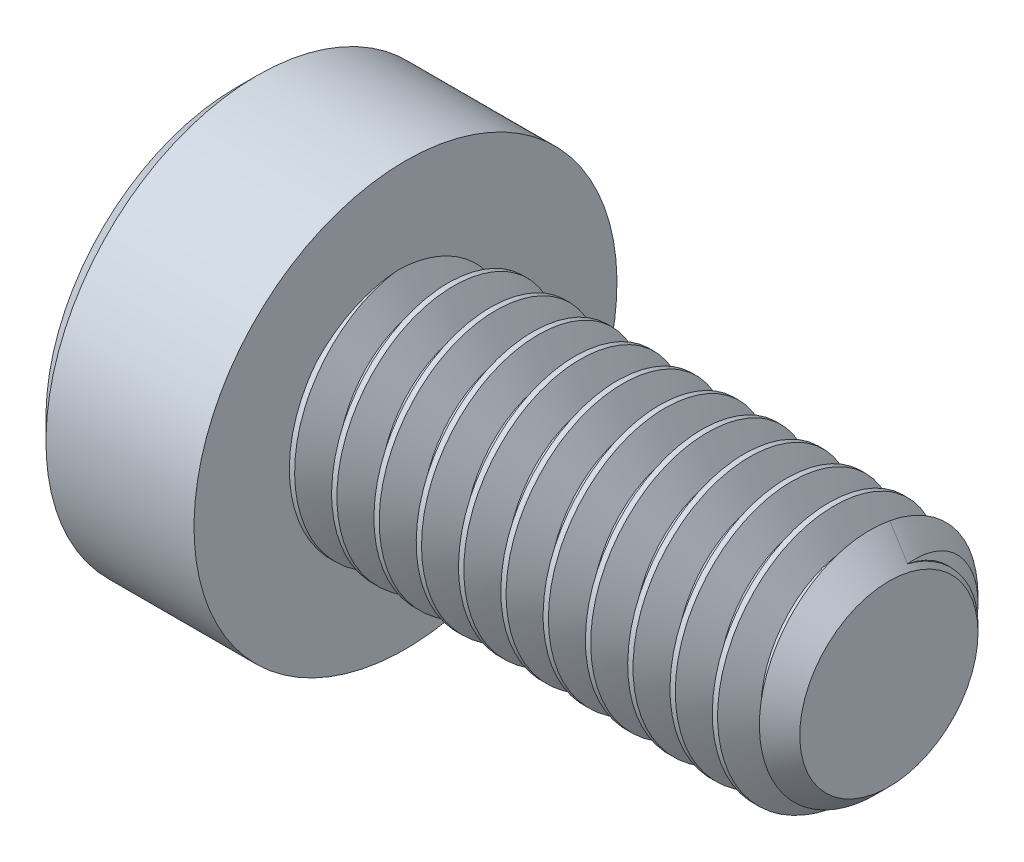
SolidWorks part; units mm, degrees
ref_plane "Front Plane" through (0, 0, 0) normal (0, 0, 1) x (1, 0, 0)
ref_plane "Top Plane" through (0, 0, 0) normal (0, 1, 0) x (1, 0, 0)
ref_plane "Right Plane" through (0, 0, 0) normal (1, 0, 0) x (0, 0, -1)
sketch "Sketch1" plane through (0, 0, 0) normal (0, 0, 1) x (1, 0, 0)
  line L0 (4, 0) -> (-4, 0) construction
  line L1 (4, 2) -> (4, -2) construction
  line L2 (-4, 3.5) -> (-4, -3.5) construction
  line L3 (-4, 3.5) -> (-6.45, 3.5) construction
  line L4 (-6.45, 3.5) -> (-6.8, 3.15) construction
  line L5 (-6.8, 3.15) -> (-6.8, -3.15) construction
  line L6 (-6.8, -3.15) -> (-6.45, -3.5) construction
  line L7 (-6.45, -3.5) -> (-4, -3.5) construction
  point P7 (-4.38, 0)
  point P12 (1.2, -2)
  dimension "D1" = 45
  dimension "Dec." = 4
  dimension "Length" = 8
  dimension "Head Dia" = 7
  dimension "Head Height" = 2.8
  dimension "Hex Depth" = 2.42
  dimension "Chamfer" = 0.35
  dimension "D2" = 2.8
ref_plane "Plane1" through (4, 0, 0) normal (1, 0, 0) x (0, 0, -1)
ref_plane "Plane2" through (-6.8, 0, 0) normal (1, 0, 0) x (0, 0, -1)
sketch "Sketch2" plane through (4, 0, 0) normal (1, 0, 0) x (0, 0, -1)
  circle A0 centre (0, 0) radius 2
extrude "Boss-Extrude1" add sketch "Sketch2" against normal up to vertex (8 mm away) up to point (-4, 0, 0)
sketch "Sketch3" plane through (4, 0, 0) normal (1, 0, 0) x (0, 0, -1)
  circle A0 centre (0, 0) radius 2 construction
  circle A1 centre (0, 0) radius 2
curve "Helix/Spiral1" pitch 0.7 height 8.7 radius 2 centre (4, 0, 0) axis (-1, 0, 0) start towards (0, 1, 0) parameters "Pitch"=0.7
chamfer "Chamfer1" distance 0.525 angle 45 1 edges at (4, 0, -2)
sketch "Sketch5" plane through (0, 0, 0) normal (0, 0, 1) x (1, 0, 0)
  line L0 (3.6938, 2) -> (4.3062, 2)
  line L1 (4.3062, 2) -> (4.0437, 1.5453)
  line L2 (4.0437, 1.5453) -> (3.9562, 1.5453)
  line L3 (3.9562, 1.5453) -> (3.6938, 2)
  line L4 (4, 1.5453) -> (4, 2) construction
  line L5 (3.825, 1.7727) -> (4.175, 1.7727) construction
  dimension "D1" = 60
  dimension "D2" = 0.35
  dimension "D3" = 0.0875
sweep "Cut-Sweep1" cut profiles "Sketch5" path "Helix/Spiral1" align with end faces yes
sketch "Sketch4" plane through (-6.8, 0, 0) normal (1, 0, 0) x (0, 0, -1)
  line L0 (-3.5, 0.7937) -> (3.5, 0.7937) construction
  line L1 (0, 1.4434) -> (-1.25, 0.7217)
  line L2 (-1.25, 0.7217) -> (-1.25, -0.7217)
  line L3 (-1.25, -0.7217) -> (0, -1.4434)
  line L4 (0, -1.4434) -> (1.25, -0.7217)
  line L5 (1.25, -0.7217) -> (1.25, 0.7217)
  line L6 (1.25, 0.7217) -> (0, 1.4434)
  line L7 (0, 0) -> (0, 0.7937) construction
  circle A0 centre (0, 0) radius 1.25 construction
  dimension "Hex Size" = 2.5
  dimension "D1" = 7
  dimension "D2" = 0.7937
sketch "Sketch6" plane through (0, 0, 0) normal (0, 0, 1) x (1, 0, 0)
  line L0 (-6.45, 3.5) -> (-6.8, 3.15) construction
  line L1 (-4, 3.5) -> (-6.45, 3.5) construction
  line L2 (-4, 3.5) -> (-4, -3.5) construction
  line L3 (-6.8, 3.15) -> (-6.8, -3.15) construction
  line L4 (-6.45, 3.5) -> (-6.8, 3.15)
  line L5 (-4, 3.5) -> (-6.45, 3.5)
  line L6 (-4, 3.5) -> (-4, 0)
  line L7 (-6.8, 3.15) -> (-6.8, 0)
  line L8 (-4, 0) -> (-6.8, 0) construction
  line L9 (-4, 0) -> (-6.8, 0)
revolve "Revolve1" add sketch "Sketch6" angle 360 about L8
extrude "Cut-Extrude1" cut sketch "Sketch4" along normal up to vertex (2.42 mm away) up to point (-4.38, 0, 0)
sketch "Sketch8" plane through (-6.8, 0, 0) normal (-1, 0, 0) x (0, 0, 1)
  circle A1 centre (0, 0) radius 1.4434
extrude "Cut-Extrude2" cut sketch "Sketch8" against normal through all draft 45
equation "\"D3@Helix/Spiral1\" = \"Length@Sketch1\"+\"Pitch@Helix/Spiral1\""
equation "\"D3@Sketch5\" = \"Pitch@Helix/Spiral1\"*.125"
equation "\"D2@Sketch5\" = \"Pitch@Helix/Spiral1\"*.50"
equation "\"D1@Chamfer1\" = \"Pitch@Helix/Spiral1\"*.75"
equation "\"D2@Sketch1\" = \"Pitch@Helix/Spiral1\"*4"
equation "\"D1@Sketch4\" = \"Head Dia@Sketch1\""
equation "\"Chamfer@Sketch1\" = \"Head Height@Sketch1\"/8"
